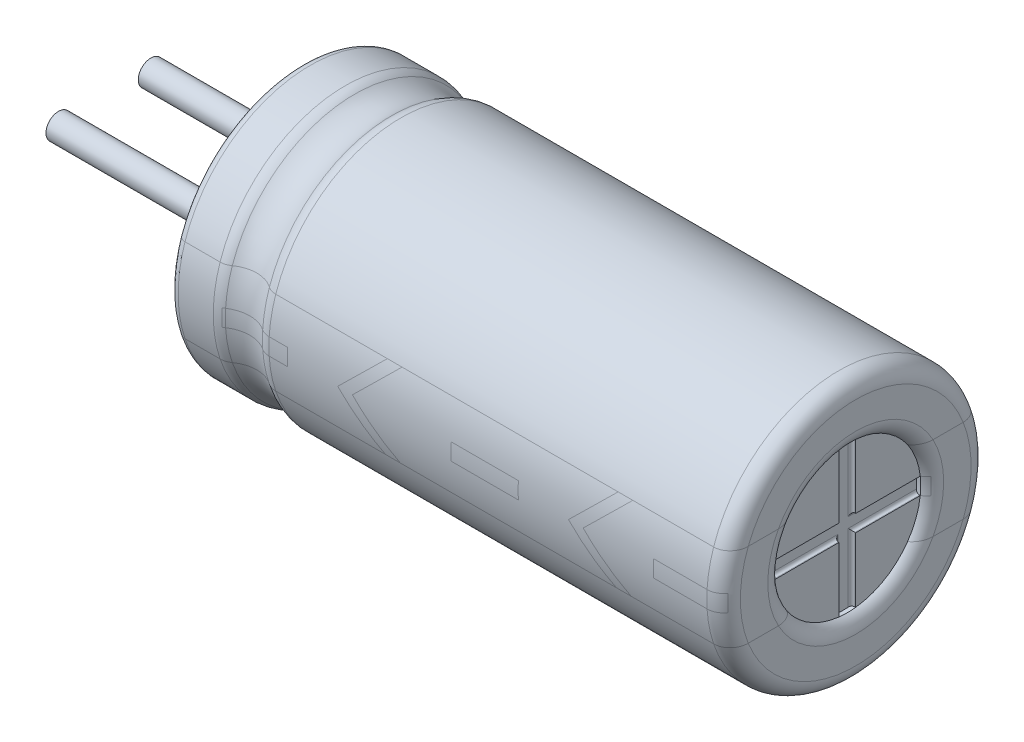
SolidWorks part; units mm, degrees
ref_plane "Front Plane" through (0, 0, 0) normal (0, 0, 1) x (1, 0, 0)
ref_plane "Top Plane" through (0, 0, 0) normal (0, 1, 0) x (1, 0, 0)
ref_plane "Right Plane" through (0, 0, 0) normal (1, 0, 0) x (0, 0, -1)
sketch "Эскиз1" plane through (0, 0, 0) normal (0, 1, 0) x (1, 0, 0)
  line L0 (-17.2337, 0) -> (16.838, 0) construction
  line L1 (0, 0) -> (0, 3.15)
  line L2 (0, 3.15) -> (1.1708, 3.15)
  line L3 (13.2, 3.15) -> (13.2, 0)
  line L4 (13.2, 0) -> (0, 0)
  line L5 (2.2292, 3.15) -> (13.2, 3.15)
  arc A0 (1.1708, 3.15) -> (2.2292, 3.15) centre (1.7, 3.75) ccw
  dimension "D3" = 1.6
  dimension "D1" = 3.15
  dimension "D2" = 13.2
  dimension "D4" = 1.7
  dimension "D5" = 0.6
revolve "Повернуть1" add sketch "Эскиз1" angle 360 about L0
fillet "Скругление1" radius 0.4 2 edges at (2.2292, 0, 3.15) (1.1708, 0, 3.15)
sketch "Эскиз2" plane through (13.2, 0, 0) normal (1, 0, 0) x (0, 0, -1)
  line L0 (0, 3.4063) -> (0, -3.6242) construction
  line L1 (-3.4972, 0) -> (3.5584, 0) construction
  circle A0 centre (0, 0) radius 1.75
  dimension "D1" = 3.5
extrude "Вырез-Вытянуть1" cut sketch "Эскиз2" against normal blind 0.2
fillet "Скругление2" radius 0.4 1 edges at (13.2, 0, -1.75)
fillet "Скругление3" radius 0.4 1 edges at (13.2, 0, 3.15)
sketch "Эскиз3" plane through (13, 0, 0) normal (1, 0, 0) x (0, 0, -1)
  line L0 (0, 3.4147) -> (0, -3.4901) construction
  line L1 (-3.5223, 0) -> (3.4327, 0) construction
  line L2 (-0.2, 1.7385) -> (-0.2, 0.2)
  line L3 (-0.2, 0.2) -> (-1.7385, 0.2)
  line L4 (0.2, 0.2) -> (1.7385, 0.2)
  line L5 (0.2, 1.7385) -> (0.2, 0.2)
  line L6 (0.2, -0.2) -> (1.7385, -0.2)
  line L7 (0.2, -1.7385) -> (0.2, -0.2)
  line L8 (-0.2, -1.7385) -> (-0.2, -0.2)
  line L9 (-0.2, -0.2) -> (-1.7385, -0.2)
  circle A0 centre (0, 0) radius 1.75 construction
  arc A1 (-1.7385, 0.2) -> (-1.7385, -0.2) centre (0, 0) ccw
  arc A2 (0.2, 1.7385) -> (-0.2, 1.7385) centre (0, 0) ccw
  arc A3 (1.7385, -0.2) -> (1.7385, 0.2) centre (0, 0) ccw
  arc A4 (-0.2, -1.7385) -> (0.2, -1.7385) centre (0, 0) ccw
  dimension "D1" = 0.2
  dimension "D2" = 0.2
extrude "Вырез-Вытянуть2" cut sketch "Эскиз3" against normal blind 0.1
sketch "Эскиз5" plane through (0, 0, 0) normal (-1, 0, 0) x (0, 0, 1)
  circle A0 centre (0, 0) radius 2.5
  dimension "D1" = 5
extrude "Вырез-Вытянуть3" cut sketch "Эскиз5" against normal blind 0.3
fillet "Скругление6" radius 0.2 2 edges at (0, 0, 2.5) (0, 0, 3.15)
sketch "Эскиз6" plane through (0.3, 0, 0) normal (-1, 0, 0) x (0, 0, 1)
  line L0 (-3.5152, 0) -> (3.4398, 0) construction
  line L1 (0, 3.3812) -> (0, -3.3644) construction
  circle A0 centre (-1.1, 0) radius 0.3
  circle A1 centre (1.1, 0) radius 0.3
  dimension "D1" = 0.6
  dimension "D2" = 1.1
extrude "Бобышка-Вытянуть1" add sketch "Эскиз6" along normal blind 5
fillet "Скругление7" radius 0.08 8 edges at (12.9, 0.9693, -0.2) (12.9, -0.9693, -0.2) (12.9, -0.2, -0.9693) (12.9, -0.2, 0.9693) (12.9, -0.9693, 0.2) (12.9, 0.9693, 0.2) (12.9, 0.2, -0.9693) (12.9, 0.2, 0.9693)
ref_plane "Плоскость1" through (0, 0, 3.5) normal (0, 0, 1) x (1, 0, 0)
sketch "Эскиз7" plane through (0, 0, 3.5) normal (0, 0, 1) x (1, 0, 0)
  line L0 (-2.8406, 0) -> (14.5012, 0) construction
  line L1 (0, 2.95) -> (0, -2.95) construction
  line L2 (-2, 1) -> (13.3536, 1)
  line L3 (-2, 1) -> (-2, -1)
  line L4 (-2, -1) -> (13.3536, -1)
  line L5 (13.3536, 1) -> (13.3536, -1)
  line L6 (10.8742, 1) -> (9.8536, 0)
  line L7 (9.8536, 0) -> (10.8334, -1)
  line L8 (10.8334, -1) -> (10.4834, -1)
  line L9 (10.4834, -1) -> (9.5036, 0)
  line L10 (9.5036, 0) -> (10.5242, 1)
  line L11 (10.5242, 1) -> (10.8742, 1)
  line L12 (5.0242, 1) -> (5.3742, 1)
  line L13 (6.7036, 0.2) -> (8.3036, 0.2)
  line L14 (6.7036, 0.2) -> (6.7036, -0.2)
  line L15 (6.7036, -0.2) -> (8.3036, -0.2)
  line L16 (8.3036, 0.2) -> (8.3036, -0.2)
  line L17 (6.7036, 0.2) -> (8.3036, -0.2) construction
  line L18 (6.7036, -0.2) -> (8.3036, 0.2) construction
  line L21 (5.3334, -1) -> (4.9834, -1)
  line L28 (-0.4758, 1) -> (-0.1258, 1)
  line L31 (-0.1666, -1) -> (-0.5166, -1)
  line L38 (-0.5166, -1) -> (-1.4964, 0) [skipped]
  line L39 (-1.1464, 0) -> (-0.1666, -1) [skipped]
  line L40 (-0.1258, 1) -> (-1.1464, 0) [skipped]
  line L41 (-1.4964, 0) -> (-0.4758, 1) [skipped]
  line L42 (1.2036, 0.2) -> (1.2036, -0.2) [skipped]
  line L43 (1.2036, -0.2) -> (2.8036, -0.2) [skipped]
  line L44 (2.8036, 0.2) -> (2.8036, -0.2) [skipped]
  line L45 (1.2036, 0.2) -> (2.8036, 0.2) [skipped]
  line L46 (4.9834, -1) -> (4.0036, 0) [skipped]
  line L47 (4.3536, 0) -> (5.3334, -1) [skipped]
  line L48 (5.3742, 1) -> (4.3536, 0) [skipped]
  line L49 (4.0036, 0) -> (5.0242, 1) [skipped]
  line L50 (1.2036, 0.2) -> (1.2036, -0.2)
  line L51 (1.2036, 0.2) -> (2.8036, 0.2)
  line L52 (2.8036, 0.2) -> (2.8036, -0.2)
  line L53 (1.2036, -0.2) -> (2.8036, -0.2)
  line L54 (5.0242, 1) -> (5.3742, 1)
  line L55 (5.3742, 1) -> (4.3536, 0)
  line L56 (4.3536, 0) -> (5.3334, -1)
  line L57 (5.3334, -1) -> (4.9834, -1)
  line L58 (4.9834, -1) -> (4.0036, 0)
  line L59 (4.0036, 0) -> (5.0242, 1)
  line L60 (11.5299, 0.2) -> (11.5299, -0.2)
  line L61 (11.5299, 0.2) -> (13.1299, 0.2)
  line L62 (13.1299, 0.2) -> (13.1299, -0.2)
  line L63 (11.5299, -0.2) -> (13.1299, -0.2)
  line L64 (-4.2964, 0.2) -> (-4.2964, -0.2) [skipped]
  line L65 (-4.2964, -0.2) -> (-2.6964, -0.2) [skipped]
  line L66 (-2.6964, 0.2) -> (-2.6964, -0.2) [skipped]
  line L67 (-4.2964, 0.2) -> (-2.6964, 0.2) [skipped]
  point P9 (13.3536, 0)
  point P12 (7.5036, 0)
  point P71 (11.5299, 0)
  point P72 (13.3536, 1)
  point P73 (0, 0)
  dimension "D2" = 2
  dimension "D3" = 2
  dimension "D4" = 0.25
  dimension "D5" = 3.5
  dimension "D6" = 1.4
  dimension "D7" = 1.6
  dimension "D8" = 0.4
  dimension "D9" = 1.2
  dimension "D12" = 1.6
  dimension "D13" = 0.4
  dimension "D10" = 3
  dimension "D11" = 2
split line "Разделяющая линия1"
